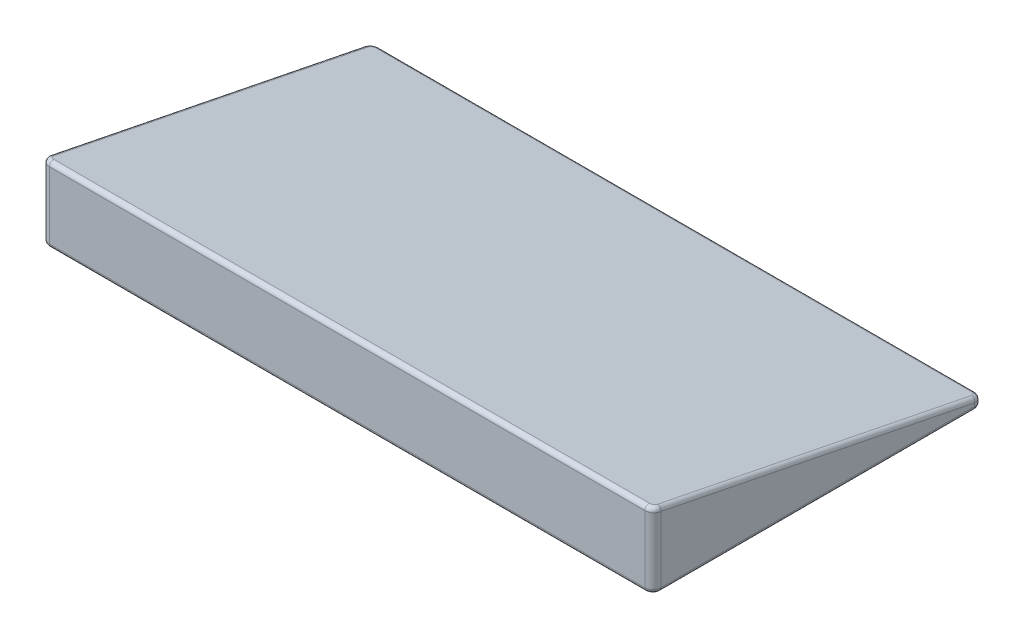
SolidWorks part; units mm, degrees
ref_plane "Front Plane" through (0, 0, 0) normal (0, 0, 1) x (1, 0, 0)
ref_plane "Top Plane" through (0, 0, 0) normal (0, 1, 0) x (1, 0, 0)
ref_plane "Right Plane" through (0, 0, 0) normal (1, 0, 0) x (0, 0, -1)
ref_plane "Plane1" through (241.3, 0, 0) normal (1, 0, 0) x (0, 0, -1)
sketch "Sketch1" plane through (241.3, 0, 0) normal (1, 0, 0) x (0, 0, -1)
  line L0 (-130.175, 0) -> (130.175, 0)
  line L1 (130.175, 0) -> (130.175, 7.62)
  line L2 (130.175, 7.62) -> (-130.175, 59.69)
  line L3 (-130.175, 59.69) -> (-130.175, 0)
extrude "Boss-Extrude1" add sketch "Sketch1" against normal blind 482.6
fillet "Fillet1" radius 6.35 4 edges at (-241.3, 3.81, -130.175) (-241.3, 29.845, 130.175) (241.3, 29.845, 130.175) (241.3, 3.81, -130.175) tangent propagation no
fillet "Fillet2" radius 3.175 16 edges at (239.4401, 0, -128.3151) (0, 0, -130.175) (241.3, 0, 0) (-239.4401, 0, -128.3151) (239.4401, 0, 128.3151) (-241.3, 0, 0) (0, 0, 130.175) (-239.4401, 0, 128.3151) (-239.4401, 59.318, 128.3151) (-241.3, 33.655, 0) (0, 59.69, 130.175) (-239.4401, 7.992, -128.3151) (239.4401, 59.318, 128.3151) (0, 7.62, -130.175) (241.3, 33.655, 0) (239.4401, 7.992, -128.3151) tangent propagation no
